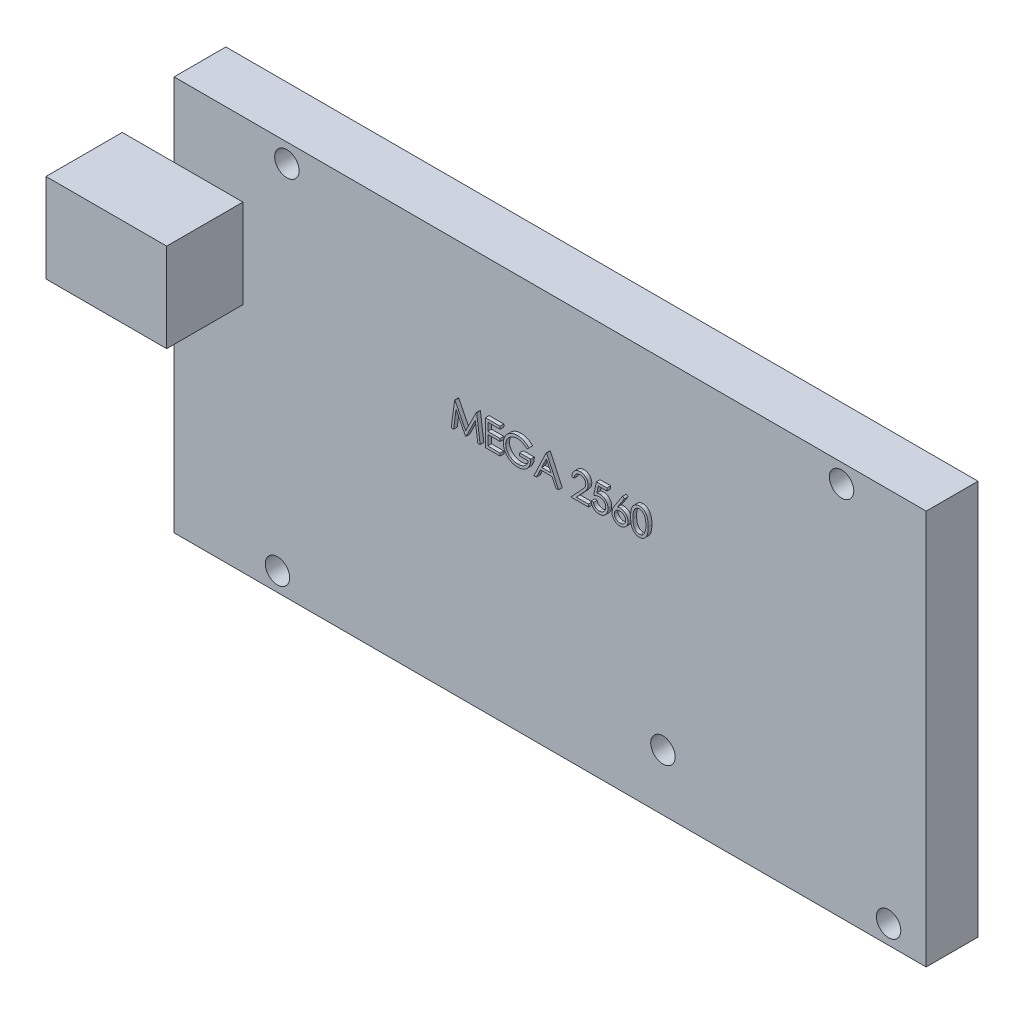
SolidWorks part; units mm, degrees
ref_plane "前视基准面" through (0, 0, 0) normal (0, 0, 1) x (1, 0, 0)
ref_plane "上视基准面" through (0, 0, 0) normal (0, 1, 0) x (1, 0, 0)
ref_plane "右视基准面" through (0, 0, 0) normal (1, 0, 0) x (0, 0, -1)
sketch "草图1" plane through (0, 0, 0) normal (0, 0, 1) x (1, 0, 0)
  line L1 (0, 0) -> (-101.6, 0)
  line L2 (0, 0) -> (0, 53.34)
  line L3 (0, 53.34) -> (-101.6, 53.34)
  line L4 (-101.6, 0) -> (-101.6, 53.34)
  line L5 (-108.6, 43.34) -> (-92.3, 43.34)
  line L6 (-108.6, 43.34) -> (-108.6, 31.34)
  line L7 (-108.6, 31.34) -> (-92.3, 31.34)
  line L8 (-92.3, 43.34) -> (-92.3, 31.34)
  circle A0 centre (-5.08, 2.54) radius 1.65
  circle A1 centre (-87.63, 2.54) radius 1.65
  circle A2 centre (-86.36, 50.8) radius 1.65
  circle A3 centre (-35.56, 7.62) radius 1.65
  circle A4 centre (-11.43, 50.8) radius 1.65
  dimension "D3" = 2.54
  dimension "D13" = 3.3
  dimension "D14" = 3.3
  dimension "D15" = 3.3
  dimension "D16" = 3.3
  dimension "D17" = 3.3
  dimension "D1" = 53.34
  dimension "D2" = 101.6
  dimension "D4" = 7.62
  dimension "D5" = 2.54
  dimension "D6" = 50.8
  dimension "D7" = 50.8
  dimension "D8" = 15.24
  dimension "D9" = 90.17
  dimension "D10" = 96.52
  dimension "D11" = 66.04
  dimension "D12" = 13.97
  dimension "D18" = 16.3
  dimension "D19" = 12
  dimension "D20" = 7
  dimension "D21" = 10
extrude "凸台-拉伸1" add sketch "草图1" against normal blind 7 contours L5 L8 L7 L4 L1 L2 L3 A4 A3 A2 A1 A0 | L8 L5 L4 L7 region at (-49.8672, 26.4748, 0) region at (-96.95, 37.34, 0)
extrude "凸台-拉伸2" add sketch "草图1<3>" along normal blind 10.3 contours L8 L5 L4 L7 | L6 L7 L4 L5 region at (-105.1, 37.34, 0) region at (-96.95, 37.34, 0)
sketch "草图1<3>" plane through (0, 0, 0) normal (0, 0, 1) x (1, 0, 0) same geometry as "草图1"
sketch "草图2" plane through (0, 0, 0) normal (0, 0, 1) x (1, 0, 0)
  text T0 "MEGA 2560"
extrude "凸台-拉伸3" add sketch "草图2" along normal blind 0.5
